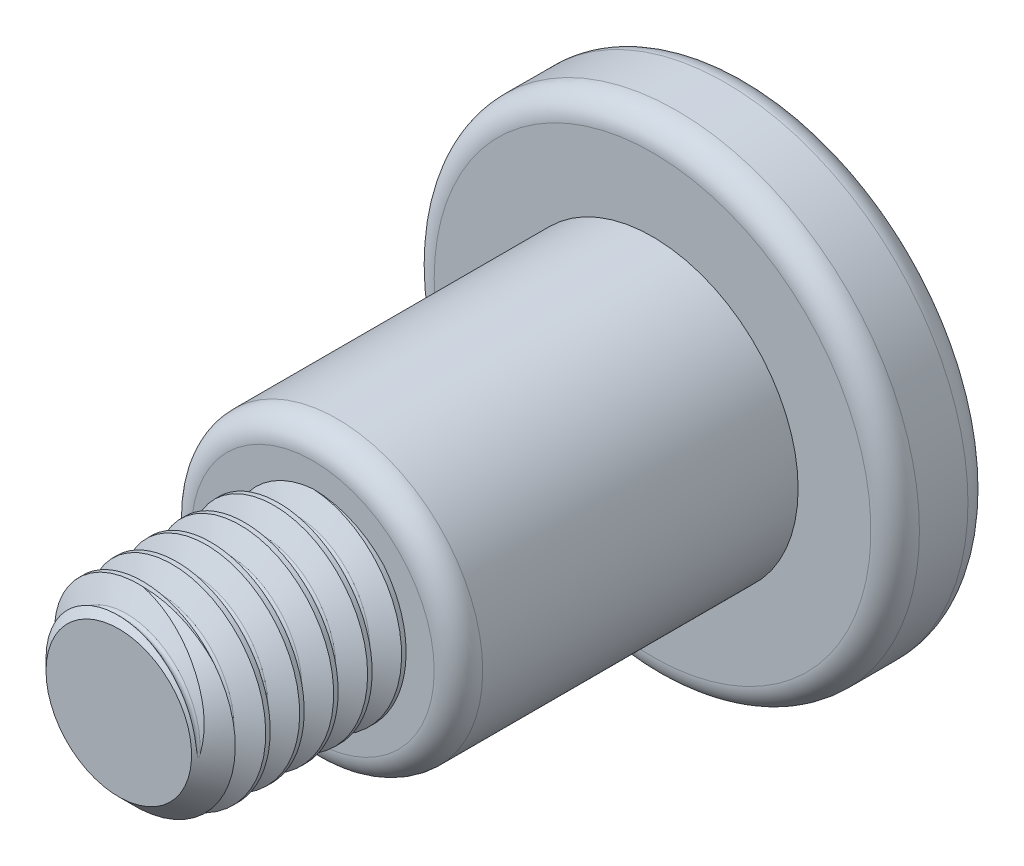
SolidWorks part; units mm, degrees
material "AR-M2"
ref_plane "正面" through (0, 0, 0) normal (0, 0, 1) x (1, 0, 0)
ref_plane "平面" through (0, 0, 0) normal (0, 1, 0) x (1, 0, 0)
ref_plane "右側面" through (0, 0, 0) normal (1, 0, 0) x (0, 0, -1)
sketch "ｽｹｯﾁ1" plane through (0, 0, 0) normal (1, 0, 0) x (0, 0, -1)
  line L0 (-4.522, 0) -> (3.5383, 0) construction
  line L1 (2, 0) -> (2, 5)
  line L2 (2, 5) -> (0, 5)
  line L3 (0, 5) -> (0, 3)
  line L4 (0, 3) -> (-7, 3)
  line L5 (-7, 3) -> (-7, 2)
  line L6 (-7, 2) -> (-11, 2)
  line L7 (-11, 2) -> (-11, 0)
  line L8 (-11, 0) -> (2, 0)
  dimension "D1" = 6
  dimension "D2" = 7
  dimension "D3" = 2
  dimension "D4" = 10
  dimension "D5" = 4
  dimension "D6" = 4
revolve "回転1" add sketch "ｽｹｯﾁ1" angle 360 about L0
fillet "ﾌｨﾚｯﾄ1" radius 0.5 3 edges at (5, 0, -2) (5, 0, 0) (3, 0, 7)
chamfer "面取り1" distance 0.5 angle 45 1 edges at (2, 0, 11)
sketch "ｽｹｯﾁ8" plane through (0, 0, 0) normal (1, 0, 0) x (0, 0, -1)
  line L0 (-11, 0) -> (-7, 0) construction
  line L1 (-11, 1.5) -> (-11, -1.5) construction
  line L2 (-7, 2) -> (-7, -2) construction
  line L3 (-10.5, 2) -> (-7, 2)
  line L4 (-7, -2) -> (-10.5, -2)
  line L5 (-7, -2) -> (-10.5, -2) construction
  line L6 (-10.5, 2) -> (-7, 2) construction
  line L7 (-7, 2.0758) -> (-10.5, 2.0758) construction
  line L8 (-7, 2.5) -> (-7, -2.5) construction
  line L9 (-7.3039, 2.0758) -> (-7.3039, 1.4736) construction
  line L10 (-7.3039, 1.4736) -> (-6.9563, 2.0758) construction
  line L11 (-6.9563, 2.0758) -> (-7.3039, 2.0758) construction
  line L12 (-7.3039, 1.4736) -> (-7.6516, 2.0758) construction
  line L13 (-7.3039, 1.4736) -> (-7, 1.4736) construction
  line L14 (-7, 1.6) -> (-10.5, 1.6) construction
  line L15 (-10.5, 2) -> (-10.5, -2) construction
  line L16 (-7.239, 1.5861) -> (-7, 2)
  line L17 (-7, 2) -> (-7.6078, 2)
  line L18 (-7.6078, 2) -> (-7.3689, 1.5861)
  arc A0 (-7.3689, 1.5861) -> (-7.239, 1.5861) centre (-7.3039, 1.6236) ccw
  point P27 (-7.6078, 2)
  dimension "D5" = 0.15
  dimension "D1" = 0.0758
  dimension "D2" = 60
  dimension "D3" = 0.6022
  dimension "D4" = 3.2
sketch "ｽｹｯﾁ9" plane through (0, 0, 7) normal (0, 0, 1) x (1, 0, 0)
  circle A0 centre (0, 0) radius 2 construction
  circle A1 centre (0, 0) radius 2
curve "ﾍﾘｶﾙ ｶｰﾌﾞ/ｽﾊﾟｲﾗﾙ ｶｰﾌﾞ1" pitch 0.7 height 5.6 radius 2 left hand yes centre (0, 0, 7) axis (0, 0, 1) start towards (0, 1, 0)
sweep "ｶｯﾄ - ｽｲｰﾌﾟ1" cut profiles "ｽｹｯﾁ8" path "ﾍﾘｶﾙ ｶｰﾌﾞ/ｽﾊﾟｲﾗﾙ ｶｰﾌﾞ1" align with end faces yes
equation "\"D1@ｽｹｯﾁ8\"=0.7/8*0.866025"
equation "\"D3@ｽｹｯﾁ8\"=0.86025*0.7"
